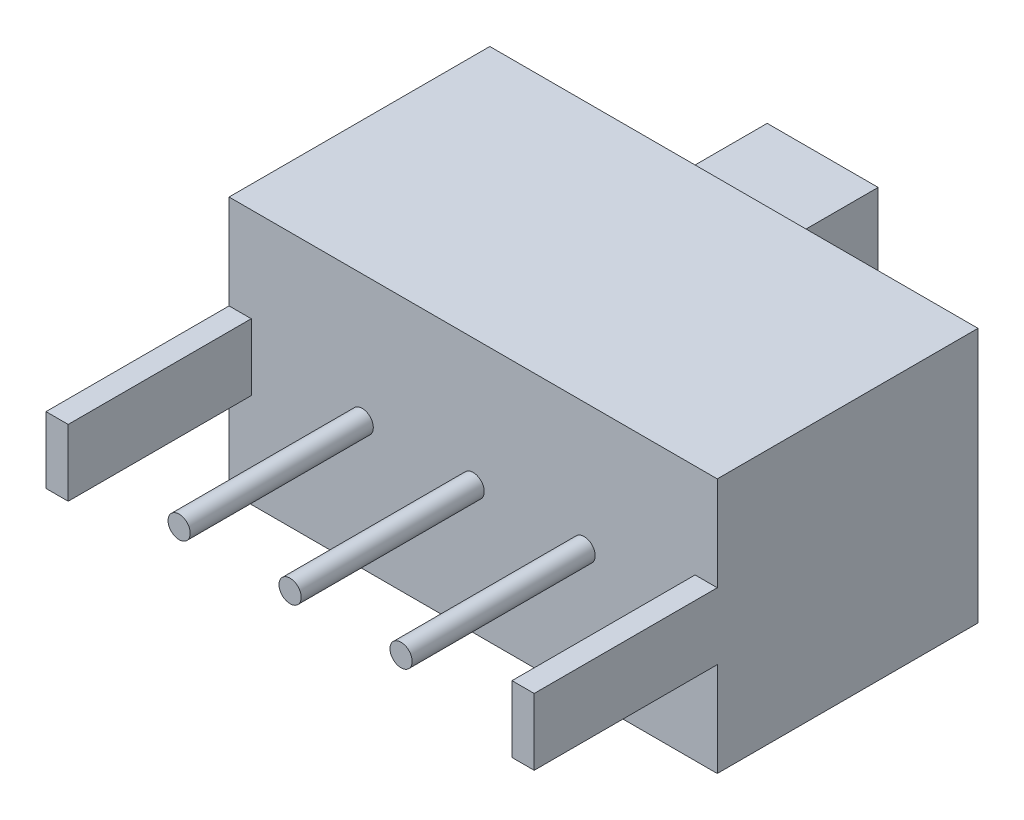
SolidWorks part; units mm, degrees
ref_plane "前视基准面" through (0, 0, 0) normal (0, 0, 1) x (1, 0, 0)
ref_plane "上视基准面" through (0, 0, 0) normal (0, 1, 0) x (1, 0, 0)
ref_plane "右视基准面" through (0, 0, 0) normal (1, 0, 0) x (0, 0, -1)
other "Configuration Table"
sketch "草图1" plane through (0, 0, 0) normal (0, 0, 1) x (1, 0, 0)
  line L1 (0, 0) -> (8.8, 0)
  line L2 (0, 0) -> (0, -4.6)
  line L3 (0, -4.6) -> (8.8, -4.6)
  line L4 (8.8, 0) -> (8.8, -4.6)
  line L5 (2.3, -1.2) -> (6.5, -1.2)
  line L6 (2.3, -1.2) -> (2.3, -3.4)
  line L7 (2.3, -3.4) -> (6.5, -3.4)
  line L8 (6.5, -1.2) -> (6.5, -3.4)
  line L9 (2.4, -1.3) -> (4.4, -1.3)
  line L10 (2.4, -1.3) -> (2.4, -3.3)
  line L11 (2.4, -3.3) -> (4.4, -3.3)
  line L12 (4.4, -1.3) -> (4.4, -3.3)
  point P13 (4.4, -4.6)
  point P14 (2.3, -2.3)
  point P15 (2.4, -2.3)
  point P16 (0, -2.3)
  point P17 (4.4, -1.2)
  dimension "D1" = 8.8
  dimension "D2" = 4.6
  dimension "D3" = 4.2
  dimension "D4" = 2.2
  dimension "D5" = 2
  dimension "D7" = 2
extrude "凸台-拉伸1" add sketch "草图1" along normal blind 4.7 contours L2 L3 L4 L1
extrude "切除-拉伸1" cut sketch "草图1<3>" along normal blind 0.2 contours L5 L8 L7 L6 | L12 L11 L10 L9
sketch "草图1<3>" plane through (0, 0, 0) normal (0, 0, 1) x (1, 0, 0) same geometry as "草图1"
extrude "凸台-拉伸2" add sketch "草图1<4>" against normal blind 2.6 contours L12 L11 L10 L9
sketch "草图1<4>" plane through (0, 0, 0) normal (0, 0, 1) x (1, 0, 0) same geometry as "草图1"
sketch "草图2" plane through (0, 0, 4.7) normal (0, 0, 1) x (1, 0, 0)
  line L5 (8.8, 0) -> (8.8, -4.6) construction
  line L6 (8.8, -1.7) -> (8.4, -1.7)
  line L7 (8.8, -1.7) -> (8.8, -2.9)
  line L8 (8.8, -2.9) -> (8.4, -2.9)
  line L9 (8.4, -1.7) -> (8.4, -2.9)
  line L11 (0, -1.7) -> (0.4, -1.7)
  line L12 (0, -1.7) -> (0, -2.9)
  line L13 (0, -2.9) -> (0.4, -2.9)
  line L14 (0.4, -1.7) -> (0.4, -2.9)
  line L15 (0, 0) -> (8.8, -4.6)
  line L17 (0, 0) -> (0, -4.6) construction
  circle A0 centre (2.4, -2.3) radius 0.2
  circle A1 centre (4.4, -2.3) radius 0.2
  circle A2 centre (6.4, -2.3) radius 0.2
  point P4 (0, -2.3)
  point P5 (8.4, -2.3)
  dimension "D3" = 0.4
  dimension "D4" = 0.4
  dimension "D1" = 2
  dimension "D2" = 2
  dimension "D5" = 1.2
extrude "凸台-拉伸3" add sketch "草图2" along normal blind 3.3 contours L13 L14 L11 L12 | A0 | A1 | A2 | L8 L9 L6 L7
